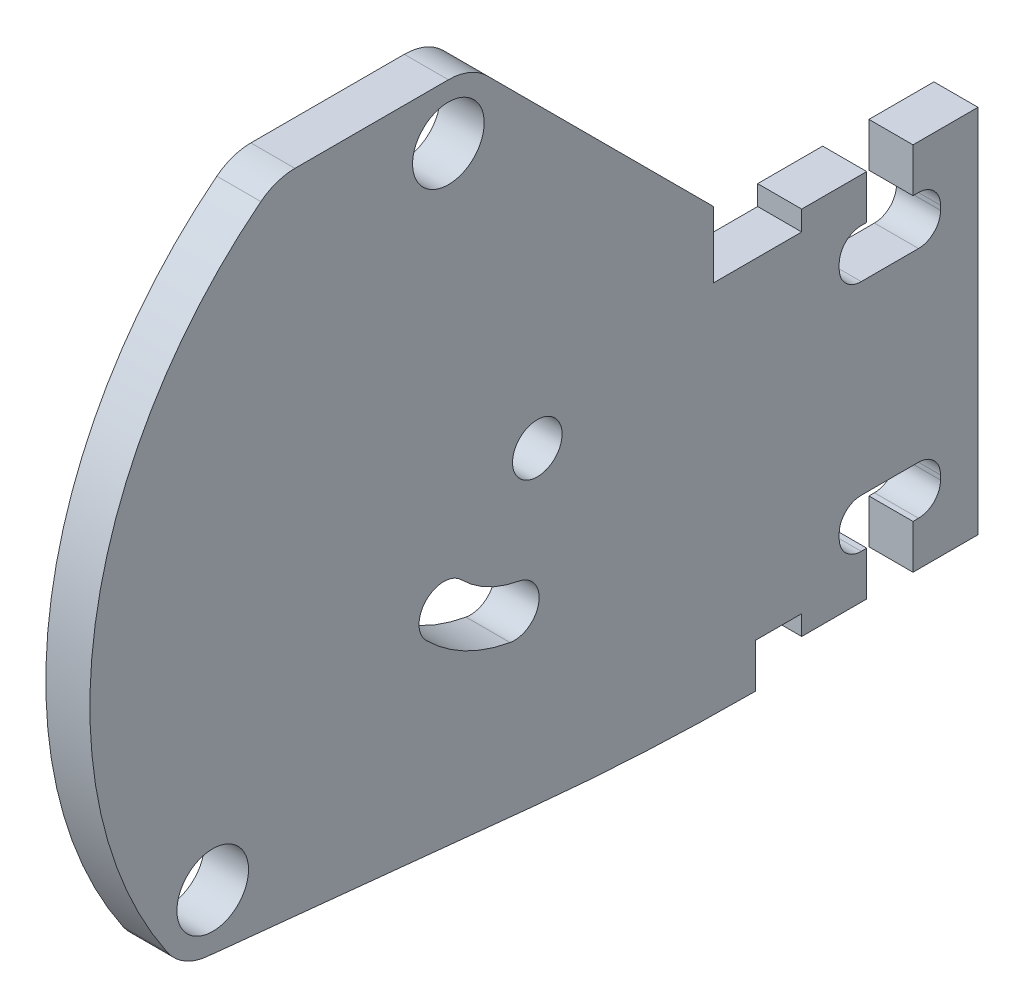
SolidWorks part; units mm, degrees
ref_plane "Front Plane" through (0, 0, 0) normal (0, 0, 1) x (1, 0, 0)
ref_plane "Top Plane" through (0, 0, 0) normal (0, 1, 0) x (1, 0, 0)
ref_plane "Right Plane" through (0, 0, 0) normal (1, 0, 0) x (0, 0, -1)
sketch "Sketch1" plane through (0, 0, 0) normal (1, 0, 0) x (0, 0, -1)
  line L0 (-16, 7.5) -> (20, 7.5) construction
  line L1 (-16, 15) -> (20, 15)
  line L2 (-16, 15) -> (-16, 0)
  line L3 (-16, 0) -> (20, 0)
  line L4 (20, 15) -> (20, 0)
  line L5 (0, 15) -> (0, 0) construction
  line L10 (0, 12.5) -> (-4.2426, 8.2574) construction
  line L11 (8, 15) -> (8, 18)
  line L12 (8, 18) -> (-5.9213, 31.9213)
  line L13 (20, 15) -> (12, 15)
  line L14 (20, 15) -> (20, 15.9)
  line L15 (20, 15.9) -> (12, 15.9)
  line L16 (12, 15) -> (12, 15.9)
  line L18 (16, 15.9) -> (16, -0.9) construction
  line L19 (20, 0) -> (12, 0)
  line L20 (20, 0) -> (20, -0.9)
  line L21 (20, -0.9) -> (12, -0.9)
  line L22 (12, 0) -> (12, -0.9)
  line L23 (14.95, 1.1) -> (17.05, 1.1)
  line L24 (14.95, 13.9) -> (17.05, 13.9)
  line L25 (14.95, 13.9) -> (14.95, 15.9)
  line L26 (14.95, 15.9) -> (17.05, 15.9)
  line L27 (17.05, 13.9) -> (17.05, 15.9)
  line L28 (14.95, 13.9) -> (17.05, 15.9) construction
  line L29 (14.95, 15.9) -> (17.05, 13.9) construction
  line L30 (13.7, 11.7) -> (18.3, 11.7)
  line L31 (13.7, 11.7) -> (13.7, 13.9)
  line L32 (13.7, 13.9) -> (18.3, 13.9)
  line L33 (18.3, 11.7) -> (18.3, 13.9)
  line L34 (13.7, 11.7) -> (18.3, 13.9) construction
  line L35 (13.7, 13.9) -> (18.3, 11.7) construction
  line L36 (14.95, 1.1) -> (14.95, -0.9)
  line L37 (14.95, -0.9) -> (17.05, -0.9)
  line L38 (17.05, 1.1) -> (17.05, -0.9)
  line L39 (13.7, 3.3) -> (13.7, 1.1)
  line L40 (13.7, 1.1) -> (18.3, 1.1)
  line L41 (18.3, 3.3) -> (18.3, 1.1)
  line L42 (13.7, 3.3) -> (18.3, 3.3)
  line L43 (-3, 29) -> (-11.8322, 29)
  line L44 (0, 12.5) -> (-1.2372, 5.4832) construction
  line L45 (4.9, -2) -> (-14.982, 0.0127)
  line L46 (9.9, 0) -> (4.9, 0)
  line L47 (9.9, 0) -> (9.9, -2)
  line L48 (9.9, -2) -> (4.9, -2)
  line L49 (4.9, 0) -> (4.9, -2)
  circle A2 centre (0, 12.5) radius 1.125
  circle A12 centre (-4.2426, 8.2574) radius 1.125
  circle A14 centre (0, 12.5) radius 20.3039
  circle A15 centre (0, 12.5) radius 4.875
  circle A16 centre (0, 12.5) radius 7.125
  circle A17 centre (-14.7303, 2.5) radius 2.5
  circle A18 centre (-14.7303, 2.5) radius 1.625
  circle A19 centre (-4.0355, 26.5) radius 2.5
  circle A20 centre (-4.0355, 26.5) radius 1.625
  circle A21 centre (-10.9991, 26.5) radius 2.5
  circle A22 centre (-1.0419, 6.5912) radius 1.125
  point P15 (16, 14.9)
  point P34 (16, 12.8)
  dimension "D1" = 2.25
  dimension "D2" = 5
  dimension "D7" = 6
  dimension "D11" = 2.1
  dimension "D16" = 5
  dimension "D17" = 3.25
  dimension "D3" = 15
  dimension "D4" = 20
  dimension "D5" = 16
  dimension "D6" = 45
  dimension "D8" = 8
  dimension "D9" = 0.9
  dimension "D10" = 8
  dimension "D12" = 2
  dimension "D13" = 2.2
  dimension "D14" = 4.6
  dimension "D15" = 3
  dimension "D18" = 14
  dimension "D19" = 10
  dimension "D20" = 0.9
  dimension "D21" = 2
  dimension "D22" = 5
  dimension "D23" = 6.1
extrude "Base shape" add sketch "Sketch1" along normal blind 2 contours A16 L1 L11 L12 A14 L2 | A16 L1 L2 L3 L36 L40 L39 L42 L41 A14 L4 L27 L32 L33 L30 L31 L25 | L1 A16 A15 | L1 A16 A12 A15 | L1 A15 A2 | L1 A15 | A16 L1 A15 | A14 L38 L3 L4 L41 L40 | L3 L38 L21 L20 | L36 L3 L22 L21 | L1 L25 L15 L16 | A18 L2 A17 | A18 L2 A17 | A19 A20 | A21 | A14 L14 L15 | L3 L49 L48 L47 | L49 L3 L45 region at (0, 14.61, -10) region at (0, 18.7739, 9.6278) region at (0, 15.45, -13.475) region at (0, 9.6923, -4.2211) region at (0, 15.1412, -5.4286) region at (0, 13.7642, -4.5815) region at (0, 15.9731, 0) region at (0, 11.886, 5.7256) region at (0, 27.4296, 1.7912) region at (0, 15.45, -18.525) region at (0, 4.6164, 13.5212) region at (0, 2.5, 16.5586) region at (0, 26.5, 10.9991) region at (0, 2.8412, -19.0769) region at (0, -0.45, -18.525) region at (0, -0.6667, 1.6855) region at (0, -1, -7.4) region at (0, -0.45, -13.475)
fillet "Bottom fillet" radius 100 1 edges at (1, -2, -4.9)
fillet "Fillet1" radius 1 8 edges at (1, 13.9, -13.7) (1, 11.7, -13.7) (1, 11.7, -18.3) (1, 13.9, -18.3) (1, 1.1, -18.3) (1, 3.3, -18.3) (1, 1.1, -13.7) (1, 3.3, -13.7)
